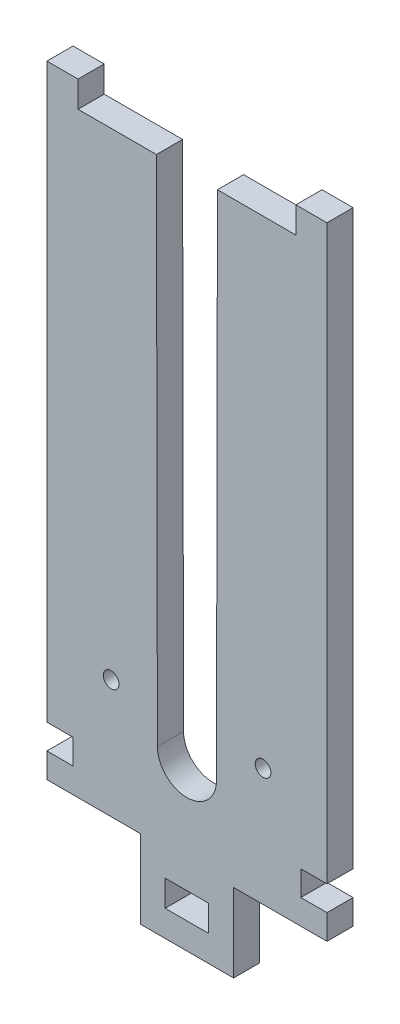
SolidWorks part; units mm, degrees
ref_plane "Front Plane" through (0, 0, 0) normal (0, 0, 1) x (1, 0, 0)
ref_plane "Top Plane" through (0, 0, 0) normal (0, 1, 0) x (1, 0, 0)
ref_plane "Right Plane" through (0, 0, 0) normal (1, 0, 0) x (0, 0, -1)
sketch "Sketch1" plane through (0, 0, 0) normal (0, 0, 1) x (1, 0, 0)
  line L1 (0, 0) -> (57.15, 0)
  line L2 (0, 0) -> (0, 127)
  line L3 (0, 127) -> (57.15, 127)
  line L4 (57.15, 0) -> (57.15, 127)
  dimension "D1" = 57.15
  dimension "D2" = 127
extrude "Boss-Extrude3" add sketch "Sketch1" along normal blind 5.334
sketch "Sketch3" plane through (0, 0, 5.334) normal (0, 0, 1) x (1, 0, 0)
  line L0 (22.352, 127) -> (0, 127)
  line L1 (57.15, 127) -> (0, 127) construction
  line L2 (57.15, 127) -> (34.798, 127)
  line L3 (28.575, 0) -> (28.575, 16.51) construction
  line L4 (0, 0) -> (57.15, 0) construction
  line L5 (34.798, 127) -> (34.6018, 22.479)
  line L6 (22.352, 127) -> (22.5482, 22.479)
  line L7 (28.575, 22.479) -> (28.575, 16.51)
  circle A0 centre (28.575, 22.479) radius 6.0268
  line M9 (57.15, 127) -> (0, 127)
  dimension "D1" = 22.352
  dimension "D2" = 22.352
  dimension "D3" = 16.51
  dimension "D4" = 5.969
extrude "Cut-Extrude2" cut sketch "Sketch3" against normal through all contours A0 L5 L6 M9 | A0 region at (28.575, 77.3496, 5.334) region at (28.575, 16.4692, 5.334)
sketch "Sketch8" plane through (0, 0, 0) normal (0, -1, 0) x (1, 0, 0)
  line L0 (0, 5.334) -> (57.15, 5.334) construction
  line L1 (57.15, 0) -> (38.1, 0)
  line L2 (57.15, 0) -> (57.15, 5.334)
  line L3 (57.15, 5.334) -> (38.1, 5.334)
  line L4 (38.1, 0) -> (38.1, 5.334)
  line L5 (0, 0) -> (57.15, 0) construction
  line L6 (19.05, 0) -> (0, 0)
  line L7 (19.05, 0) -> (19.05, 5.334)
  line L8 (19.05, 5.334) -> (0, 5.334)
  line L9 (0, 0) -> (0, 5.334)
  line L10 (38.1, 5.334) -> (19.05, 5.334) construction
extrude "Cut-Extrude6" cut sketch "Sketch8" against normal blind 5.334 contours L4 L3 L2 L1
extrude "Cut-Extrude7" cut sketch "Sketch8<5>" against normal blind 5.334
sketch "Sketch8<5>" plane through (0, 0, 0) normal (0, -1, 0) x (1, 0, 0) same geometry as "Sketch8"
sketch "Sketch16" plane through (0, 127, 0) normal (0, 1, 0) x (1, 0, 0)
  line L1 (34.798, 0) -> (57.15, 0)
  line L2 (34.798, 0) -> (34.798, -5.334)
  line L3 (34.798, -5.334) -> (57.15, -5.334)
  line L4 (57.15, 0) -> (57.15, -5.334)
  line L5 (0, 0) -> (22.352, 0)
  line L6 (0, 0) -> (0, -5.334)
  line L7 (0, -5.334) -> (22.352, -5.334)
  line L8 (22.352, 0) -> (22.352, -5.334)
extrude "Boss-Extrude4" add sketch "Sketch16" along normal blind 5.334
sketch "Sketch32" plane through (0, 132.334, 0) normal (0, 1, 0) x (1, 0, 0)
  line L0 (0, -5.334) -> (22.352, -5.334) construction
  line L1 (0, 0) -> (6.35, 0)
  line L2 (0, 0) -> (0, -5.334)
  line L3 (0, -5.334) -> (6.35, -5.334)
  line L4 (6.35, 0) -> (6.35, -5.334)
  line L5 (34.798, -5.334) -> (57.15, -5.334) construction
  line L6 (57.15, 0) -> (50.8, 0)
  line L7 (57.15, 0) -> (57.15, -5.334)
  line L8 (57.15, -5.334) -> (50.8, -5.334)
  line L9 (50.8, 0) -> (50.8, -5.334)
  line L11 (6.35, 0) -> (22.352, 0)
  line L12 (6.35, 0) -> (6.35, -5.334)
  line L13 (6.35, -5.334) -> (22.352, -5.334)
  line L14 (22.352, 0) -> (22.352, -5.334)
  line L15 (34.798, -5.334) -> (50.8, -5.334)
  line L16 (34.798, -5.334) -> (34.798, 0)
  line L17 (34.798, 0) -> (50.8, 0)
  line L18 (50.8, -5.334) -> (50.8, 0)
  line M4 (0, -5.334) -> (22.352, -5.334)
  line M5 (22.352, -5.334) -> (22.352, 0)
  line M6 (22.352, 0) -> (0, 0)
  dimension "D1" = 6.35
  dimension "D2" = 6.35
extrude "Cut-Extrude13" cut sketch "Sketch32" against normal blind 5.334 contours L4 M6 M4 M5 | L17 L16 L15 L9 region at (14.351, 132.334, 2.667) region at (42.799, 132.334, 2.667)
sketch "Sketch35" plane through (0, 0, 5.334) normal (0, 0, 1) x (1, 0, 0)
  circle A0 centre (13.1076, 29.5507) radius 1.6
  circle A1 centre (44.1073, 29.4071) radius 1.6
extrude "Cut-Extrude15" cut sketch "Sketch35" against normal through all
sketch "Sketch36" plane through (0, 0, 0) normal (0, -1, 0) x (1, 0, 0)
  line L1 (38.1, 0) -> (19.05, 0)
  line L2 (38.1, 0) -> (38.1, 5.334)
  line L3 (38.1, 5.334) -> (19.05, 5.334)
  line L4 (19.05, 0) -> (19.05, 5.334)
extrude "Boss-Extrude5" add sketch "Sketch36" along normal blind 10.668
sketch "Sketch37" plane through (0, 0, 0) normal (0, 0, -1) x (-1, 0, 0)
  line L0 (-19.05, -10.668) -> (-38.1, -10.668) construction
  line L1 (-33.02, 0) -> (-24.13, 0)
  line L2 (-33.02, 0) -> (-33.02, -5.334)
  line L3 (-33.02, -5.334) -> (-24.13, -5.334)
  line L4 (-24.13, 0) -> (-24.13, -5.334)
  line L5 (-19.05, 5.334) -> (-19.05, -10.668) construction
  dimension "D1" = 5.334
  dimension "D2" = 5.334
  dimension "D3" = 8.89
  dimension "D4" = 5.08
extrude "Cut-Extrude16" cut sketch "Sketch37" against normal through all
sketch "Sketch38" plane through (0, 0, 0) normal (0, 0, -1) x (-1, 0, 0)
  line L0 (-57.15, 5.334) -> (0, 5.334) construction
  line L1 (-28.575, 5.334) -> (-28.575, 13.6237) construction
  line L2 (-57.15, 5.334) -> (-57.15, 132.334) construction
  line L3 (-57.15, 10.414) -> (-51.816, 10.414)
  line L4 (-57.15, 10.414) -> (-57.15, 15.494)
  line L5 (-57.15, 15.494) -> (-51.816, 15.494)
  line L6 (-51.816, 10.414) -> (-51.816, 15.494)
  line L7 (-5.334, 10.414) -> (-5.334, 15.494)
  line L8 (0, 15.494) -> (-5.334, 15.494)
  line L9 (0, 10.414) -> (0, 15.494)
  line L10 (0, 10.414) -> (-5.334, 10.414)
  dimension "D1" = 5.334
  dimension "D2" = 5.08
  dimension "D3" = 5.08
extrude "Cut-Extrude17" cut sketch "Sketch38" against normal through all
equation "\"Foamcore\" = .1875in"
equation "\"Mdf\"= .21in"
equation "\"Gmaterial\"= \"Mdf\""
equation "\"D1@Boss-Extrude3\"= \"Gmaterial\""
equation "\"D1@Cut-Extrude6\"= \"Gmaterial\""
equation "\"D1@Cut-Extrude7\"=\"Gmaterial\""
equation "\"D1@Boss-Extrude4\"= \"Gmaterial\""
equation "\"D3@Sketch3\"= .65in"
equation "\"D1@Cut-Extrude13\"=\"Gmaterial\""
